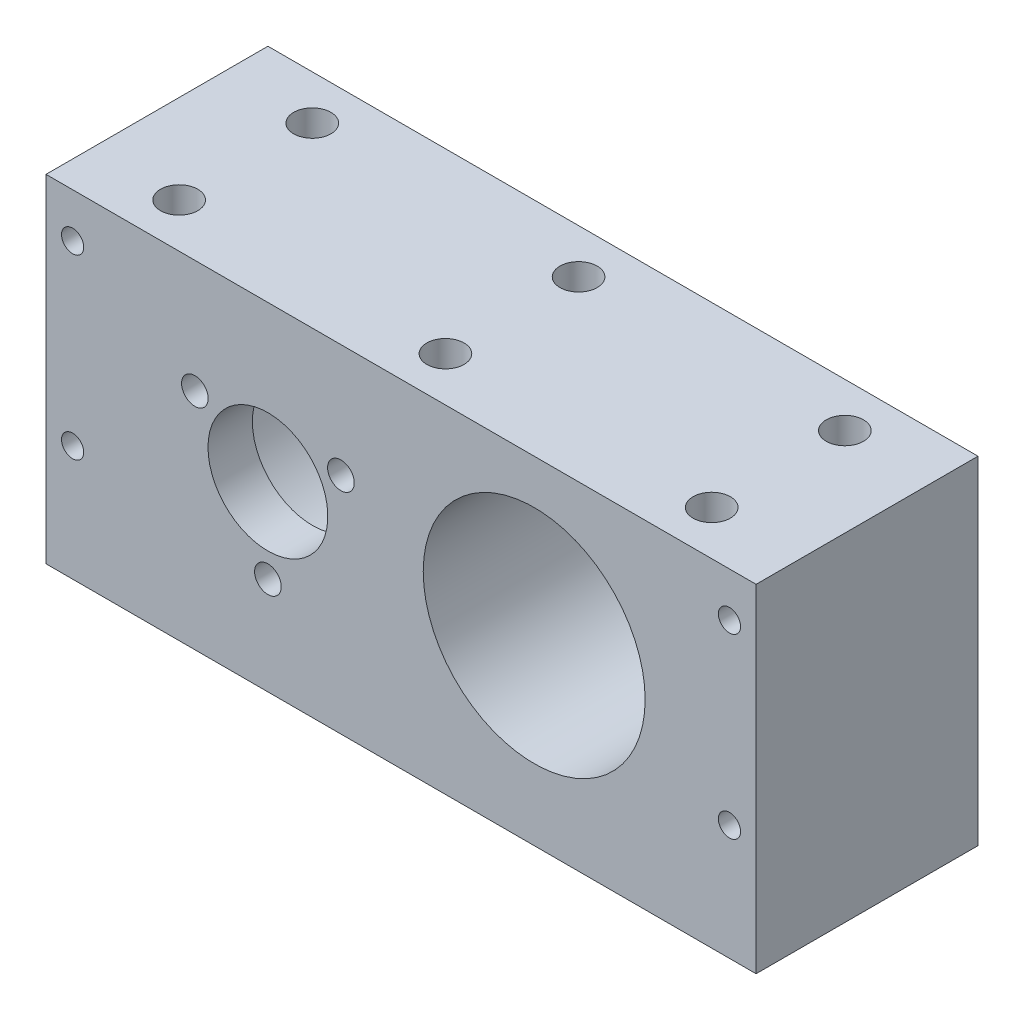
SolidWorks part; units mm, degrees
ref_plane "前视基准面" through (0, 0, 0) normal (0, 0, 1) x (1, 0, 0)
ref_plane "上视基准面" through (0, 0, 0) normal (0, 1, 0) x (1, 0, 0)
ref_plane "右视基准面" through (0, 0, 0) normal (1, 0, 0) x (0, 0, -1)
other "Configuration Table"
sketch "草图1" plane through (0, 0, 0) normal (0, 0, 1) x (1, 0, 0)
  line L1 (-35, 17.5) -> (35, 17.5)
  line L2 (-35, 17.5) -> (-35, -17.5)
  line L3 (-35, -17.5) -> (35, -17.5)
  line L4 (35, 17.5) -> (35, -17.5)
  line L5 (0, -17.5) -> (0, 17.5) construction
  line L6 (-35, 0) -> (35, 0) construction
  point P0 (0, 0)
  dimension "D1" = 70
  dimension "D2" = 35
extrude "凸台-拉伸1" add sketch "草图1" along normal blind 25
sketch "草图2" plane through (0, 17.5, 0) normal (0, 1, 0) x (1, 0, 0)
  line L0 (0, 0) -> (0, -25) construction
  line L1 (35, -25) -> (-35, -25) construction
  line L3 (30, -5) -> (-30, -5) construction
  line L4 (30, -5) -> (30, -20) construction
  line L5 (30, -20) -> (-30, -20) construction
  line L6 (-30, -5) -> (-30, -20) construction
  line L7 (0, -20) -> (0, -5) construction
  line L8 (30, -12.5) -> (-30, -12.5) construction
  circle A0 centre (30, -5) radius 2.1
  circle A1 centre (30, -20) radius 2.1
  circle A2 centre (-30, -5) radius 2.1
  circle A3 centre (-30, -20) radius 2.1
  point P5 (0, -12.5)
  dimension "D3" = 4.2
  dimension "D1" = 60
  dimension "D2" = 15
extrude "切除-拉伸1" cut sketch "草图2" against normal blind 10
sketch "草图3" plane through (0, 0, 0) normal (0, 0, -1) x (-1, 0, 0)
  line L0 (-35, 0) -> (35, 0) construction
  line L1 (-35, -17.5) -> (-35, 17.5) construction
  line L2 (35, 17.5) -> (35, -17.5) construction
  circle A0 centre (15, 0) radius 12.5
  dimension "D1" = 25
  dimension "D2" = 20
extrude "切除-拉伸2" cut sketch "草图3" against normal blind 20
sketch "草图5" plane through (0, 0, 20) normal (0, 0, -1) x (-1, 0, 0)
  circle A0 centre (15, 0) radius 6.75
  dimension "D1" = 13.5
extrude "切除-拉伸4" cut sketch "草图5" against normal blind 5
sketch "草图6" plane through (0, 0, 20) normal (0, 0, -1) x (-1, 0, 0)
  line L0 (15, 0) -> (15, -9.5) construction
  line L1 (15, 0) -> (15, -9.5) construction
  circle A0 centre (15, 0) radius 9.5 construction
  circle A1 centre (15, -9.5) radius 1.5
  circle A2 centre (6.7728, 4.75) radius 1.5
  circle A3 centre (23.2272, 4.75) radius 1.5
  point P13 (15, 0)
  dimension "D1" = 19
  dimension "D2" = 3
  dimension "D3" = 0
  dimension "D4" = 3
extrude "切除-拉伸5" cut sketch "草图6" against normal blind 5
sketch "草图8" plane through (0, 0, 25) normal (0, 0, 1) x (1, 0, 0)
  line L0 (35, 0) -> (-35, 0) construction
  line L1 (35, -17.5) -> (35, 17.5) construction
  line L2 (-35, 17.5) -> (-35, -17.5) construction
  circle A0 centre (15, 0) radius 12.5
  dimension "D1" = 25
  dimension "D2" = 20
extrude "切除-拉伸6" cut sketch "草图8" against normal blind 20
sketch "草图9" plane through (0, 0, 5) normal (0, 0, 1) x (1, 0, 0)
  circle A0 centre (15, 0) radius 6.75
  dimension "D1" = 13.5
extrude "切除-拉伸7" cut sketch "草图9" against normal blind 20
sketch "草图10" plane through (0, 0, 5) normal (0, 0, 1) x (1, 0, 0)
  line L0 (15, 0) -> (24.5, 0) construction
  line L1 (15, 0) -> (15, -9.5) construction
  circle A0 centre (15, 0) radius 9.5 construction
  circle A1 centre (15, -9.5) radius 1.5
  circle A2 centre (6.7728, 4.75) radius 1.5
  circle A3 centre (23.2272, 4.75) radius 1.5
  point P12 (15, 0)
  dimension "D1" = 19
  dimension "D3" = 3
  dimension "D2" = 90
  dimension "D4" = 3
extrude "切除-拉伸8" cut sketch "草图10" against normal through all
sketch "草图11" plane through (0, -17.5, 0) normal (0, -1, 0) x (1, 0, 0)
  line L0 (35, 12.5) -> (-35, 12.5) construction
  line L1 (35, 25) -> (35, 0) construction
  line L2 (-35, 25) -> (-35, 0) construction
  line L3 (0, 25) -> (0, 0) construction
  line L4 (-35, 25) -> (35, 25) construction
  circle A0 centre (22, 12.5) radius 3.4
  circle A2 centre (-22, 12.5) radius 3.4
  circle A3 centre (0, 12.5) radius 30 construction
  dimension "D1" = 6.8
  dimension "D2" = 22
  dimension "D3" = 60
extrude "切除-拉伸9" cut sketch "草图11" against normal blind 2
sketch "草图13" plane through (0, -17.5, 0) normal (0, -1, 0) x (1, 0, 0)
  line L1 (35, 25) -> (-35, 25)
  line L2 (35, 25) -> (35, 0)
  line L3 (35, 0) -> (-35, 0)
  line L4 (-35, 25) -> (-35, 0)
  circle A0 centre (-22, 12.5) radius 3.4 construction
  circle A1 centre (22, 12.5) radius 3.4 construction
  circle A2 centre (-22, 12.5) radius 3.4
  circle A3 centre (22, 12.5) radius 3.4
extrude "凸台-拉伸3" add sketch "草图13" along normal blind 3
sketch "草图15" plane through (-35, 0, 0) normal (-1, 0, 0) x (0, 0, 1)
  line L4 (0, 17.5) -> (0, -20.5)
  line L5 (0, -20.5) -> (25, -20.5)
  line L6 (25, -20.5) -> (25, 17.5)
  line L7 (25, 17.5) -> (0, 17.5)
  line L8 (0, 17.5) -> (0, -20.5)
  line L9 (0, -20.5) -> (25, -20.5)
  line L10 (25, -20.5) -> (25, 17.5)
  line L11 (25, 17.5) -> (0, 17.5)
  dimension "D1" = 0
extrude "凸台-拉伸4" add sketch "草图15" along normal blind 5
sketch "草图16" plane through (35, 0, 0) normal (1, 0, 0) x (0, 0, -1)
  line L4 (0, -20.5) -> (0, 17.5)
  line L5 (0, 17.5) -> (-25, 17.5)
  line L6 (-25, 17.5) -> (-25, -20.5)
  line L7 (-25, -20.5) -> (0, -20.5)
  line L8 (0, -20.5) -> (0, 17.5)
  line L9 (0, 17.5) -> (-25, 17.5)
  line L10 (-25, 17.5) -> (-25, -20.5)
  line L11 (-25, -20.5) -> (0, -20.5)
  dimension "D1" = 0
extrude "凸台-拉伸5" add sketch "草图16" along normal blind 5
sketch "草图17" plane through (0, -20.5, 0) normal (0, -1, 0) x (1, 0, 0)
  line L0 (0, 25) -> (0, 0) construction
  line L1 (40, 25) -> (-40, 25) construction
  line L2 (-40, 0) -> (40, 0) construction
  line L3 (-40, 12.5) -> (40, 12.5) construction
  line L4 (-40, 0) -> (-40, 25) construction
  line L5 (40, 25) -> (40, 0) construction
  circle A1 centre (0, 5) radius 2.1
  circle A2 centre (0, 20) radius 2.1
  dimension "D1" = 4.2
  dimension "D2" = 5
extrude "切除-拉伸11" cut sketch "草图17" against normal through all
sketch "草图18" plane through (0, 0, 0) normal (0, 0, -1) x (-1, 0, 0)
  line L0 (-37, -20.5) -> (-37, 17.5) construction
  line L1 (40, -20.5) -> (-40, -20.5) construction
  line L2 (-40, 17.5) -> (40, 17.5) construction
  line L3 (-40, -20.5) -> (-40, 17.5) construction
  circle A0 centre (-37, 12.5) radius 1.25
  circle A1 centre (-37, -7.5) radius 1.25
  dimension "D4" = 2.5
  dimension "D5" = 2.5
  dimension "D1" = 3
  dimension "D2" = 20
  dimension "D3" = 5
extrude "切除-拉伸12" cut sketch "草图18" against normal blind 5
ref_plane "基准面1" through (0, 0, 12.5) normal (0, 0, 1) x (1, 0, 0)
mirror "镜向1" about plane through (0, 0, 12.5) normal (0, 0, 1) of "切除-拉伸12"
mirror "镜向2" about plane through (0, 0, 0) normal (1, 0, 0) of "镜向1"
